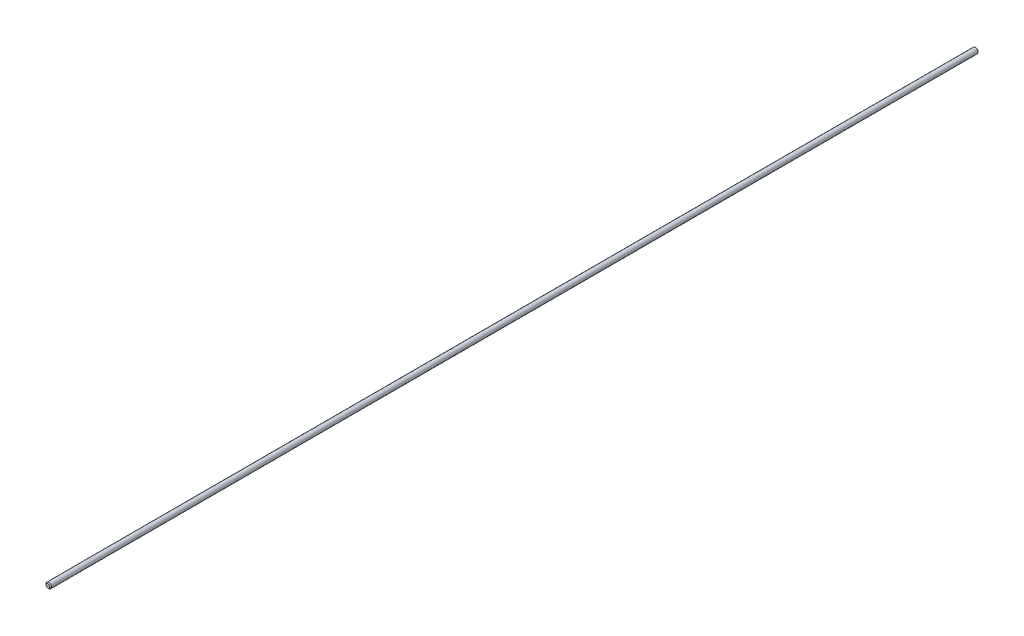
SolidWorks part; units mm, degrees
material "AISI 316 Stainless Steel Sheet (SS)"
ref_plane "Front Plane" through (0, 0, 0) normal (0, 0, 1) x (1, 0, 0)
ref_plane "Top Plane" through (0, 0, 0) normal (0, 1, 0) x (1, 0, 0)
ref_plane "Right Plane" through (0, 0, 0) normal (1, 0, 0) x (0, 0, -1)
sketch "Sketch1" plane through (0, 0, 0) normal (1, 0, 0) x (0, 0, -1)
  line L0 (-267.3477, 0) -> (267.3477, 0) construction
  line L1 (-267.3477, 0) -> (-267.3477, 1.5875)
  line L2 (-267.3477, 1.5875) -> (267.3477, 1.5875)
  line L3 (267.3477, 1.5875) -> (267.3477, 0)
  line L4 (267.943, 1.1063) -> (267.6255, 1.6562) construction
  line L5 (267.6255, 1.6562) -> (267.308, 1.1063) construction
  line L6 (267.308, 1.1063) -> (267.943, 1.1063) construction
  line L7 (267.9033, 1.1751) -> (267.3477, 1.1751) construction
  line L8 (267.6255, 1.1063) -> (267.6255, 1.1751) construction
  line L9 (267.6255, 1.1751) -> (267.6255, 1.5875) construction
  line L10 (267.6255, 1.5875) -> (267.6255, 1.6562) construction
  line L15 (267.6652, 1.5875) -> (267.5858, 1.5875)
  line L16 (267.9232, 1.1407) -> (267.3279, 1.1407)
  line L17 (267.5858, 1.5875) -> (267.3279, 1.1407)
  line L18 (267.6652, 1.5875) -> (267.9232, 1.1407)
  line L19 (267.3477, 0) -> (267.3477, -1.5875) construction
  point P17 (267.6255, 1.1407)
  point P18 (254.6477, 0)
  point P19 (266.0777, -1.5875)
  point P20 (241.9477, 0)
  point P22 (-254.6477, 0)
  dimension "Length" = 534.6954
  dimension "Thread size" = 3.175
  dimension "Pitch" = 0.635
  dimension "D2" = 0.0794
  dimension "D1" = 1.27
  dimension "Segment" = 25.4
  dimension "D3" = 12.7
  dimension "D4" = 12.7
sketch "Sketch2" plane through (0, 0, 0) normal (1, 0, 0) x (0, 0, -1)
  line L0 (267.3477, 1.5875) -> (267.3477, 0) construction
  line L1 (-267.3477, 1.5875) -> (267.3477, 1.5875) construction
  line L2 (-267.3477, 0) -> (-267.3477, 1.5875) construction
  line L3 (267.3477, 1.5875) -> (267.3477, 0)
  line L4 (-267.3477, 1.5875) -> (267.3477, 1.5875)
  line L5 (-267.3477, 0) -> (-267.3477, 1.5875)
  line L6 (-267.3477, 0) -> (267.3477, 0)
revolve "Revolve1" add sketch "Sketch2" angle 360 about L6
chamfer "Chamfer1" distance 0.4763 angle 45 2 edges at (1.5875, 0, -267.3477) (1.5875, 0, 267.3477)
sketch "Sketch3" [suppressed] plane through (0, 0, -304.8) normal (0, 0, -1) x (-1, 0, 0)
  circle A0 centre (0, 0) radius 1.1751
extrude "Cut-Extrude1" [suppressed] cut sketch "Sketch3" against normal through all flip side to cut
sketch "Sketch4" [suppressed] plane through (0, 0, -304.8) normal (0, 0, -1) x (-1, 0, 0)
  circle A1 centre (0, 0) radius 1.1751
  circle A2 centre (0, 0) radius 1.1751
  dimension "D1" = 0
ref_plane "Plane1" [suppressed] through (0, 0, 304.8) normal (0, 0, 1) x (1, 0, 0)
curve "Helix/Spiral1" [suppressed] pitch 0.635 height 26.035 turns 41
sketch "Sketch5" [suppressed] plane through (0, 0, 0) normal (1, 0, 0) x (0, 0, -1)
  line L0 (305.1175, 1.5875) -> (305.0381, 1.5875) construction
  line L1 (305.0381, 1.5875) -> (304.7802, 1.1407) construction
  line L2 (305.3755, 1.1407) -> (304.7802, 1.1407) construction
  line L3 (305.1175, 1.5875) -> (305.3755, 1.1407) construction
  line L4 (305.1175, 1.5875) -> (305.0381, 1.5875)
  line L5 (305.0381, 1.5875) -> (304.7802, 1.1407)
  line L6 (305.3755, 1.1407) -> (304.7802, 1.1407)
  line L7 (305.1175, 1.5875) -> (305.3755, 1.1407)
sweep "Sweep1" [suppressed] add profiles "Sketch5" path "Helix/Spiral1"
pattern_linear "LPattern1" [suppressed] count 22 spacing 25.4 along (0, 0, 1) of bodies 136
other "SurfaceCut1" [suppressed]
sketch "Sketch6" [suppressed] plane through (0, 0, 0) normal (1, 0, 0) x (0, 0, -1)
  line L0 (304.8, 1.1112) -> (304.3237, 1.5875)
  line L1 (304.8, 1.5875) -> (304.8, 0) construction
  line L3 (-304.8, 1.5875) -> (304.8, 1.5875) construction
  line L4 (304.3237, 1.5875) -> (304.3238, 1.6562)
  line L5 (304.3238, 1.6562) -> (305.3953, 1.6562)
  line L6 (305.3953, 1.6562) -> (305.3953, 1.1112)
  line L7 (305.3953, 1.1112) -> (304.8, 1.1112)
  dimension "D1" = 45
  dimension "D2" = 0.4763
revolve "Cut-Revolve1" [suppressed] cut sketch "Sketch6" angle 360 about L0
mirror "Mirror1" [suppressed] about plane through (0, 0, 0) normal (0, 0, 1)
sketch "Sketch7" plane through (0, 0, -267.3477) normal (0, 0, -1) x (-1, 0, 0)
  circle A0 centre (0, 0) radius 6.5324
extrude "Cut-Extrude2" [suppressed] cut sketch "Sketch7" against normal blind 35.306
ref_axis "Axis1" through (0, 0, 312.5597) along (0, 0, -1)
equation "\"D2@Sketch1\"=\"Pitch@Sketch1\"/8"
equation "\"D2@Sketch1\" = \"Pitch@Sketch1\" / 8"
equation "\"D1@Sketch1\"=\"Pitch@Sketch1\"*2"
equation "\"Segment@Sketch1\" = \"Pitch@Sketch1\" * 40"
equation "\"D4@Sketch1\"=\"D3@Sketch1\""
equation "\"D1@Chamfer1\"=\"pitch@sketch1\"*0.75"
equation "\"D3@Helix/Spiral1\"=\"segment@sketch1\"+\"pitch@sketch1\""
equation "\"D4@Helix/Spiral1\"=\"pitch@sketch1\""
equation "\"D3@LPattern1\"=\"segment@sketch1\""
equation "\"D1@LPattern1\"=\"length@sketch1\"/\"segment@sketch1\"+1"
equation "\"D2@Sketch6\"=\"pitch@sketch1\"*0.75"
equation "\"Length@Sketch1\"=18.0000in+4.5-1.876+0.5-.705-0.125+0.656+0.5-0.25-0.25+(0.375-0.024)-0.25"
